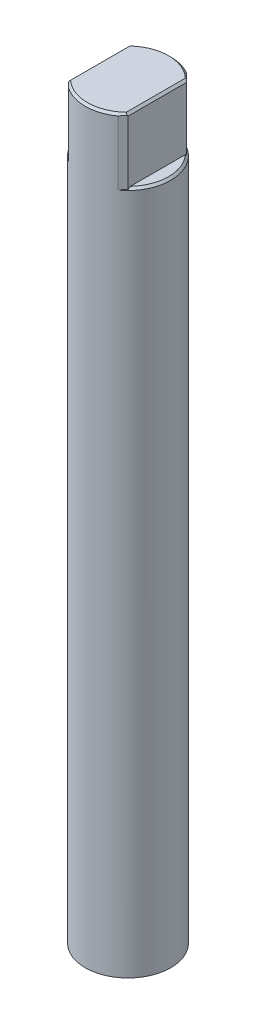
SolidWorks part; units mm, degrees
ref_plane "정면" through (0, 0, 0) normal (0, 0, 1) x (1, 0, 0)
ref_plane "윗면" through (0, 0, 0) normal (0, 1, 0) x (1, 0, 0)
ref_plane "우측면" through (0, 0, 0) normal (1, 0, 0) x (0, 0, -1)
sketch "스케치1" plane through (0, 0, 0) normal (0, 1, 0) x (1, 0, 0)
  circle A0 centre (0, 0) radius 10
  dimension "D1" = 20
extrude "보스-돌출1" add sketch "스케치1" along normal blind 175
cosmetic thread "나사산 표시1" parameters "D1"=160, "D2"=19
sketch "스케치2" plane through (0, 175, 0) normal (0, 1, 0) x (1, 0, 0)
  line L1 (-14.535, 13.4466) -> (-7, 13.4466)
  line L2 (-14.535, 13.4466) -> (-14.535, -12.4052)
  line L3 (-14.535, -12.4052) -> (-7, -12.4052)
  line L4 (-7, 13.4466) -> (-7, -12.4052)
  line L5 (14.535, 13.4466) -> (7, 13.4466)
  line L6 (14.535, 13.4466) -> (14.535, -12.4052)
  line L7 (14.535, -12.4052) -> (7, -12.4052)
  line L8 (7, 13.4466) -> (7, -12.4052)
  dimension "D1" = 7
  dimension "D2" = 7
extrude "컷-돌출1" cut sketch "스케치2" against normal blind 15
sketch "스케치5" plane through (0, 0, 0) normal (0, -1, 0) x (-1, 0, 0)
  point P0 (0, 0)
hole_wizard "M8 나사 구멍1" positions "스케치5" profile "스케치4" tap size "M8" standard "ISO"
sketch "스케치4" plane through (0, 0, 0) normal (1, 0, 0) x (0, 0, -1)
  line L0 (0, 0) -> (0, 14.0429)
  line L1 (0, 14.0429) -> (3.4, 12)
  line L2 (3.4, 12) -> (3.4, 0)
  line L5 (3.4, 0) -> (0, 0)
  line L10 (0, 14.0429) -> (-3.4, 12) construction
  line L11 (0, -6.35) -> (0, 107.95) construction
  dimension "탭 드릴 지름" = 6.8
  dimension "탭 드릴 깊이" = 12
  dimension "드릴 각도" = 118
cosmetic thread "구멍 나사산1" parameters "D1"=16, "D2"=8
chamfer "모따기1" distance 0.5 angle 45 4 edges at (0, 175, -10) (-7, 175, 0) (0, 175, 10) (7, 175, 0)
chamfer "모따기4" distance 0.2 angle 45 2 edges at (-7, 167.25, 7.1414) (7, 167.25, 7.1414) first distance on face at (-7, 167.25, 0) first distance on face at (7, 167.25, 0)
chamfer "모따기5" distance 0.5 angle 45 2 edges at (7, 167.25, -7.1414) (-7, 167.25, -7.1414) first distance on face at (7, 167.25, -0.1) first distance on face at (-7, 167.25, -0.1)
chamfer "모따기2" distance 0.5 angle 45 2 edges at (-9.9879, 160, -0.4909) (9.9879, 160, -0.4909)
